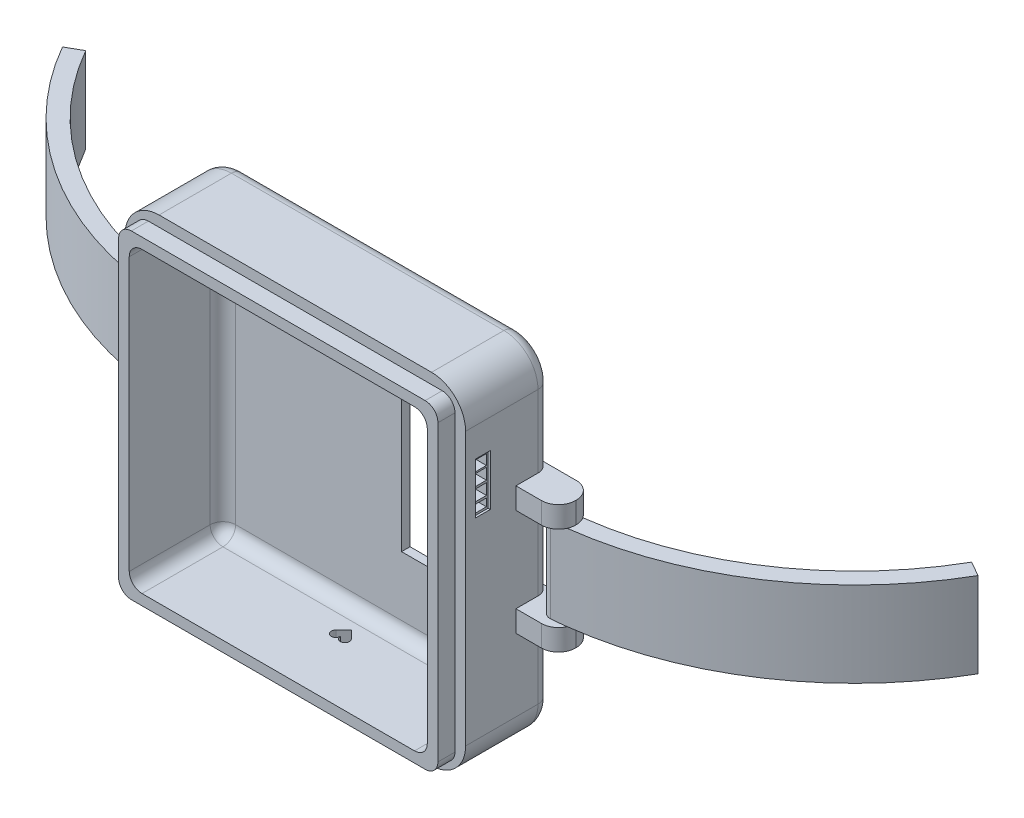
SolidWorks part; units mm, degrees
material "ABS"
ref_plane "Plan de face" through (0, 0, 0) normal (0, 0, 1) x (1, 0, 0)
ref_plane "Plan de dessus" through (0, 0, 0) normal (0, 1, 0) x (1, 0, 0)
ref_plane "Plan de droite" through (0, 0, 0) normal (1, 0, 0) x (0, 0, -1)
sketch "Esquisse1" plane through (0, 0, 0) normal (0, 0, 1) x (1, 0, 0)
  line L1 (-40, 40) -> (40, 40)
  line L2 (-40, 40) -> (-40, -40)
  line L3 (-40, -40) -> (40, -40)
  line L4 (40, 40) -> (40, -40)
  line L5 (-40, 40) -> (40, -40) construction
  line L6 (-40, -40) -> (40, 40) construction
  point P0 (0, 0)
  dimension "D1" = 80
  dimension "D2" = 80
extrude "Boss.-Extru.1" add sketch "Esquisse1" along normal blind 20
fillet "Congé1" radius 8 4 edges at (40, -40, 10) (-40, -40, 10) (-40, 40, 10) (40, 40, 10)
sketch "Esquisse2" plane through (0, 0, 20) normal (0, 0, 1) x (1, 0, 0)
  line L1 (-35, 35) -> (35, 35)
  line L2 (-35, 35) -> (-35, -35)
  line L3 (-35, -35) -> (35, -35)
  line L4 (35, 35) -> (35, -35)
  line L5 (-35, 35) -> (35, -35) construction
  line L6 (-35, -35) -> (35, 35) construction
  point P0 (0, 0)
  dimension "D1" = 70
  dimension "D2" = 70
extrude "Enlèv. mat.-Extru.1" cut sketch "Esquisse2" against normal blind 18
sketch "Esquisse3" plane through (0, 0, 2) normal (0, 0, 1) x (1, 0, 0)
  line L0 (35, 35) -> (-35, 35) construction
  line L1 (6.9612, 18) -> (31.9101, 18)
  line L2 (6.9612, 18) -> (6.9612, -18)
  line L3 (6.9612, -18) -> (31.9101, -18)
  line L4 (31.9101, 18) -> (31.9101, -18)
  line L5 (-35, -35) -> (35, -35) construction
  dimension "D1" = 17
  dimension "D2" = 17
extrude "Enlèv. mat.-Extru.2" cut sketch "Esquisse3" against normal through all
sketch "Esquisse4" plane through (0, 0, 20) normal (0, 0, 1) x (1, 0, 0)
  line L1 (-35, 35) -> (35, 35)
  line L2 (-35, 35) -> (-35, -35)
  line L3 (-35, -35) -> (35, -35)
  line L4 (35, 35) -> (35, -35)
  line L5 (-35, 35) -> (35, -35) construction
  line L6 (-35, -35) -> (35, 35) construction
  line L7 (-37.5, 37.5) -> (37.5, 37.5)
  line L8 (-37.5, 37.5) -> (-37.5, -37.5)
  line L9 (-37.5, -37.5) -> (37.5, -37.5)
  line L10 (37.5, 37.5) -> (37.5, -37.5)
  line L11 (-37.5, 37.5) -> (37.5, -37.5) construction
  line L12 (-37.5, -37.5) -> (37.5, 37.5) construction
  point P0 (0, 0)
  point P7 (0, 0)
  dimension "D1" = 2.5
extrude "Boss.-Extru.2" add sketch "Esquisse4" along normal blind 4
sketch "Esquisse5" plane through (40, 0, 0) normal (1, 0, 0) x (0, 0, -1)
  line L1 (0, -15) -> (-8.18, -15)
  line L3 (0, 15) -> (-8.18, 15)
  line L4 (-8.18, -15) -> (-8.18, 15)
  line L5 (4.9488, -0.356) -> (-8.18, 15) construction
  line L6 (4.9488, -0.356) -> (-8.18, -15) construction
  line L7 (0, -15) -> (0, 15)
  line L8 (0, 32) -> (-20, 32) construction
  line L9 (-20, -32) -> (0, -32) construction
  line L10 (0, -32) -> (0, 32) construction
  dimension "D1" = 17
  dimension "D2" = 17
  dimension "D3" = 30
  dimension "D4" = 0
  dimension "D5" = 8.18
extrude "Boss.-Extru.3" add sketch "Esquisse5" along normal blind 10
sketch "Esquisse6" plane through (50, 0, 0) normal (1, 0, 0) x (0, 0, -1)
  line L0 (-8.18, 15) -> (-8.18, -15) construction
  line L1 (-8.18, 10) -> (0, 10)
  line L2 (-8.18, 10) -> (-8.18, -10)
  line L3 (-8.18, -10) -> (0, -10)
  line L4 (0, 10) -> (0, -10)
  line L5 (0, -15) -> (0, 15) construction
  line L6 (0, 15) -> (-8.18, 15) construction
  line L7 (-8.18, -15) -> (0, -15) construction
  dimension "D1" = 5
  dimension "D2" = 5
extrude "Enlèv. mat.-Extru.4" cut sketch "Esquisse6" against normal blind 10
fillet "Congé3" radius 4 4 edges at (50, -12.5, 0) (50, -12.5, 8.18) (50, 12.5, 0) (50, 12.5, 8.18)
sketch "Esquisse7" plane through (0, 10, 0) normal (0, -1, 0) x (-1, 0, 0)
  circle A0 centre (-46, -4.18) radius 2
  dimension "D1" = 4
extrude "Boss.-Extru.4" add sketch "Esquisse7" along normal up to next
mirror "Symétrie1" about plane through (0, 0, 0) normal (1, 0, 0) of "Boss.-Extru.3", "Enlèv. mat.-Extru.4", "Congé3", "Boss.-Extru.4"
fillet "Congé4" radius 3 4 edges at (-37.5, 37.5, 22) (-37.5, -37.5, 22) (37.5, -37.5, 22) (37.5, 37.5, 22)
fillet "Congé5" radius 3 4 edges at (35, -35, 13) (35, 35, 13) (-35, 35, 13) (-35, -35, 13)
fillet "Congé6" radius 3 8 edges at (34.1213, 34.1213, 2) (35, 0, 2) (34.1213, -34.1213, 2) (0, -35, 2) (-34.1213, -34.1213, 2) (-35, 0, 2) (-34.1213, 34.1213, 2) (0, 35, 2)
fillet "Congé7" radius 3 12 edges at (40, 23.5, 0) (37.6569, 37.6569, 0) (-40, 23.5, 0) (-37.6569, 37.6569, 0) (-40, -23.5, 0) (-37.6569, -37.6569, 0) (40, -23.5, 0) (37.6569, -37.6569, 0) (40, 0, 0) (-40, 0, 0) (0, 40, 0) (0, -40, 0)
sketch "Esquisse13" plane through (0, -40, 0) normal (0, -1, 0) x (-1, 0, 0)
  line L0 (0, -27.0258) -> (0, 23.2252) construction
  line L1 (1.8193, -8.6679) -> (0, -6.8487)
  line L2 (0, -6.8487) -> (-1.8193, -8.6679)
  arc A0 (1.8193, -8.6679) -> (0, -9.4215) centre (1.0657, -9.4215) cw
  arc A1 (0, -9.4215) -> (-1.8193, -8.6679) centre (-1.0657, -9.4215) cw
extrude "Enlèv. mat.-Extru.8" cut sketch "Esquisse13" against normal blind 5
sketch "Esquisse14" plane through (-40, 0, 0) normal (-1, 0, 0) x (0, 0, 1)
  line L1 (9.1403, -19.4136) -> (16.1403, -19.4136)
  line L2 (9.1403, -19.4136) -> (9.1403, -29.4136)
  line L3 (9.1403, -29.4136) -> (16.1403, -29.4136)
  line L4 (16.1403, -19.4136) -> (16.1403, -29.4136)
  line L5 (9.1403, -19.4136) -> (16.1403, -29.4136) construction
  line L6 (9.1403, -29.4136) -> (16.1403, -19.4136) construction
  point P0 (12.6403, -24.4136)
  dimension "D1" = 10
  dimension "D2" = 7
extrude "Boss.-Extru.7" add sketch "Esquisse14" along normal blind 5
fillet "Congé10" radius 2 4 edges at (-42.5, -19.4136, 9.1403) (-42.5, -29.4136, 9.1403) (-42.5, -29.4136, 16.1403) (-42.5, -19.4136, 16.1403)
sketch "Esquisse16" plane through (-45, 0, 0) normal (-1, 0, 0) x (0, 0, 1)
  line L0 (16.1403, -24.4136) -> (-6.0395, -24.4136) construction
  line L1 (16.1403, -27.4136) -> (16.1403, -21.4136) construction
  line L2 (12.6403, -29.4136) -> (12.6403, -12.6183) construction
  line L3 (11.1403, -29.4136) -> (14.1403, -29.4136) construction
  line L5 (15.1778, -20.5434) -> (10.1028, -20.5434)
  line L6 (15.1778, -20.5434) -> (15.1778, -28.2838)
  line L7 (15.1778, -28.2838) -> (10.1028, -28.2838)
  line L8 (10.1028, -20.5434) -> (10.1028, -28.2838)
  line L9 (15.1778, -20.5434) -> (10.1028, -28.2838) construction
  line L10 (15.1778, -28.2838) -> (10.1028, -20.5434) construction
  point P8 (12.6403, -24.4136)
extrude "Enlèv. mat.-Extru.9" cut sketch "Esquisse16" against normal blind 4.5
fillet "Congé11" radius 1 4 edges at (-42.75, -28.2838, 10.1028) (-42.75, -28.2838, 15.1778) (-42.75, -20.5434, 10.1028) (-42.75, -20.5434, 15.1778)
sketch "Esquisse17" plane through (-40.5, 0, 0) normal (-1, 0, 0) x (0, 0, 1)
  line L0 (12.6403, -20.5434) -> (12.6403, -28.2838)
  line L1 (14.1778, -20.5434) -> (11.1028, -20.5434) construction
  line L2 (11.1028, -28.2838) -> (14.1778, -28.2838) construction
  line L3 (12.6403, -28.2838) -> (9.5542, -28.2838)
  line L4 (9.5542, -28.2838) -> (9.5542, -20.5434)
  line L5 (9.5542, -20.5434) -> (12.6403, -20.5434)
extrude "Boss.-Extru.8" add sketch "Esquisse17" along normal blind 4
sketch "Esquisse19" plane through (0, 0, 12.6403) normal (0, 0, 1) x (1, 0, 0)
  line L0 (-40.5, -28.2838) -> (-40.5, -20.5434) construction
  line L1 (-40.5, -23.8097) -> (-43.8654, -23.8097)
  line L2 (-40.5, -23.8097) -> (-40.5, -24.8097)
  line L3 (-40.5, -24.8097) -> (-43.8654, -24.8097)
  line L5 (-43.8654, -21.7665) -> (-43.8654, -22.7665)
  line L7 (-43.8654, -27.8963) -> (-43.8654, -28.8963)
  line L9 (-40.5, -22.7665) -> (-40.5, -21.7665)
  line L10 (-40.5, -21.7665) -> (-43.8654, -21.7665)
  line L12 (-40.5, -22.7665) -> (-43.8654, -22.7665)
  line L14 (-40.5, -26.853) -> (-43.8654, -26.853)
  line L15 (-40.5, -26.853) -> (-40.5, -25.853)
  line L16 (-40.5, -25.853) -> (-43.8654, -25.853)
  line L17 (-40.5, -26.353) -> (-43.8654, -26.353) construction
  line L18 (-40.5, -22.2665) -> (-43.8654, -22.2665) construction
  line L19 (-40.5, -27.8963) -> (-43.8654, -27.8963)
  line L21 (-40.5, -28.8963) -> (-43.8654, -28.8963)
  line L22 (-40.5, -28.8963) -> (-40.5, -27.8963)
  line L23 (-40.5, -19.7232) -> (-43.8654, -19.7232)
  line L25 (-40.5, -20.7232) -> (-43.8654, -20.7232)
  line L26 (-40.5, -20.7232) -> (-40.5, -19.7232)
  line L27 (-43.8654, -19.7232) -> (-43.8654, -20.7232)
  line L28 (-43.8654, -25.853) -> (-43.8654, -26.853)
  line L29 (-43.8654, -24.3097) -> (-39.6456, -24.3097) construction
  line L31 (-43.8654, -23.8097) -> (-43.8654, -24.8097)
extrude "Boss.-Extru.9" add sketch "Esquisse19" along normal blind 1
chamfer "Chanfrein2" distance 0.5 angle 45 5 edges at (-43.8654, -28.0901, 13.6403) (-43.8654, -26.353, 13.6403) (-43.8654, -24.3097, 13.6403) (-43.8654, -20.6333, 13.6403) (-43.8654, -22.2665, 13.6403)
sketch "Esquisse20" plane through (0, -10, 0) normal (0, 1, 0) x (1, 0, 0)
  line L0 (104.0383, 34.8201) -> (107.5105, 32.8341)
  arc A0 (46.1628, -6.1734) -> (45.8372, -2.1866) centre (46, -4.18) cw
  arc A1 (46.1628, -6.1734) -> (107.5105, 32.8341) centre (39.8152, 71.5546) ccw
  arc A2 (45.8372, -2.1866) -> (104.0383, 34.8201) centre (39.8152, 71.5546) ccw
extrude "Boss.-Extru.10" add sketch "Esquisse20" along normal blind 20
mirror "Symétrie2" about plane through (0, 0, 0) normal (1, 0, 0) of "Boss.-Extru.10"
sketch "Esquisse21" plane through (0, -40, 0) normal (0, -1, 0) x (-1, 0, 0)
  line L0 (32, -20) -> (-32, -20) construction
  line L1 (14.1445, -12.75) -> (6.6445, -12.75)
  line L2 (14.1445, -12.75) -> (14.1445, -6.25)
  line L3 (14.1445, -6.25) -> (6.6445, -6.25)
  line L4 (6.6445, -12.75) -> (6.6445, -6.25)
  line L5 (14.1445, -12.75) -> (6.6445, -6.25) construction
  line L6 (14.1445, -6.25) -> (6.6445, -12.75) construction
  point P0 (10.3945, -9.5)
  dimension "D1" = 7.5
  dimension "D2" = 10.5
  dimension "6.5" = 6.5
extrude "Enlèv. mat.-Extru.10" cut sketch "Esquisse21" against normal blind 4.5
chamfer "Chanfrein3" distance 2 angle 45 2 edges at (-6.6445, -37.75, 12.75) (-14.1445, -37.75, 12.75)
sketch "Esquisse22" plane through (0, -35.5, 0) normal (0, -1, 0) x (-1, 0, 0)
  line L1 (12.1445, -10.161) -> (8.6445, -10.161)
  line L2 (12.1445, -10.161) -> (12.1445, -7.9889)
  line L3 (12.1445, -7.9889) -> (8.6445, -7.9889)
  line L4 (8.6445, -10.161) -> (8.6445, -7.9889)
  line L5 (12.1445, -10.161) -> (8.6445, -7.9889) construction
  line L6 (12.1445, -7.9889) -> (8.6445, -10.161) construction
  point P0 (10.3945, -9.0749)
extrude "Boss.-Extru.11" add sketch "Esquisse22" along normal blind 5
sketch "Esquisse23" plane through (0, 0, 10.161) normal (0, 0, 1) x (1, 0, 0)
  line L1 (-11.4866, -35.5781) -> (-10.5329, -35.5781)
  line L2 (-11.4866, -35.5781) -> (-11.4866, -39.8726)
  line L3 (-11.4866, -39.8726) -> (-10.5329, -39.8726)
  line L4 (-10.5329, -35.5781) -> (-10.5329, -39.8726)
  line L5 (-10.0946, -35.5781) -> (-9.2051, -35.5781)
  line L6 (-10.0946, -35.5781) -> (-10.0946, -39.8726)
  line L7 (-10.0946, -39.8726) -> (-9.2051, -39.8726)
  line L8 (-9.2051, -35.5781) -> (-9.2051, -39.8726)
extrude "Boss.-Extru.12" add sketch "Esquisse23" along normal blind 0.6
chamfer "Chanfrein4" distance 2 angle 45 2 edges at (-9.6498, -39.8726, 10.761) (-11.0098, -39.8726, 10.761)
sketch "Esquisse24" plane through (0, -40, 0) normal (0, -1, 0) x (-1, 0, 0)
  circle A0 centre (-20.8771, -10.0285) radius 1.5
  dimension "D1" = 3
extrude "Enlèv. mat.-Extru.11" cut sketch "Esquisse24" against normal blind 4
sketch "Esquisse25" plane through (40, 0, 0) normal (1, 0, 0) x (0, 0, -1)
  line L1 (-17.6777, 25.1812) -> (-14.2058, 25.1812)
  line L2 (-17.6777, 25.1812) -> (-17.6777, 13.2034)
  line L3 (-17.6777, 13.2034) -> (-14.2058, 13.2034)
  line L4 (-14.2058, 25.1812) -> (-14.2058, 13.2034)
extrude "Enlèv. mat.-Extru.12" cut sketch "Esquisse25" against normal blind 5
sketch "Esquisse26" plane through (36, 0, 0) normal (1, 0, 0) x (0, 0, -1)
  line L6 (-14.2058, 13.2034) -> (-14.2058, 25.1812) construction
  line L11 (-17.6777, 25.1812) -> (-14.2058, 25.1812)
  line L12 (-17.6777, 25.1812) -> (-17.6777, 13.2135)
  line L13 (-17.6777, 13.2135) -> (-14.2058, 13.2135)
  line L14 (-14.2058, 25.1812) -> (-14.2058, 13.2135)
  line L16 (-17.1795, 24.5167) -> (-14.6055, 24.5167)
  line L17 (-17.1795, 24.5167) -> (-17.1795, 13.7018)
  line L18 (-17.1795, 13.7018) -> (-14.6055, 13.7018)
  line L19 (-14.6055, 24.5167) -> (-14.6055, 13.7018)
  line L20 (-17.1795, 22.1028) -> (-14.6055, 22.1028)
  line L21 (-17.1795, 22.1028) -> (-17.1795, 21.7391)
  line L22 (-17.1795, 21.7391) -> (-14.6055, 21.7391)
  line L23 (-14.6055, 22.1028) -> (-14.6055, 21.7391)
  line L24 (-17.1795, 19.1092) -> (-14.6055, 19.1092)
  line L25 (-17.1795, 19.1092) -> (-17.1795, 18.6168)
  line L26 (-17.1795, 18.6168) -> (-14.6055, 18.6168)
  line L27 (-14.6055, 19.1092) -> (-14.6055, 18.6168)
  line L28 (-17.1795, 16.0094) -> (-14.6055, 16.0094)
  line L29 (-17.1795, 16.0094) -> (-17.1795, 15.5013)
  line L30 (-17.1795, 15.5013) -> (-14.6055, 15.5013)
  line L31 (-14.6055, 16.0094) -> (-14.6055, 15.5013)
extrude "Boss.-Extru.13" add sketch "Esquisse26" along normal blind 3.5 contours L13 L16 L19 L18 L17 | L20 L23 L22 L21 | L26 L27 L24 L25 | L28 L31 L30 L29 region at (36, 25.0566, 15.9418)
